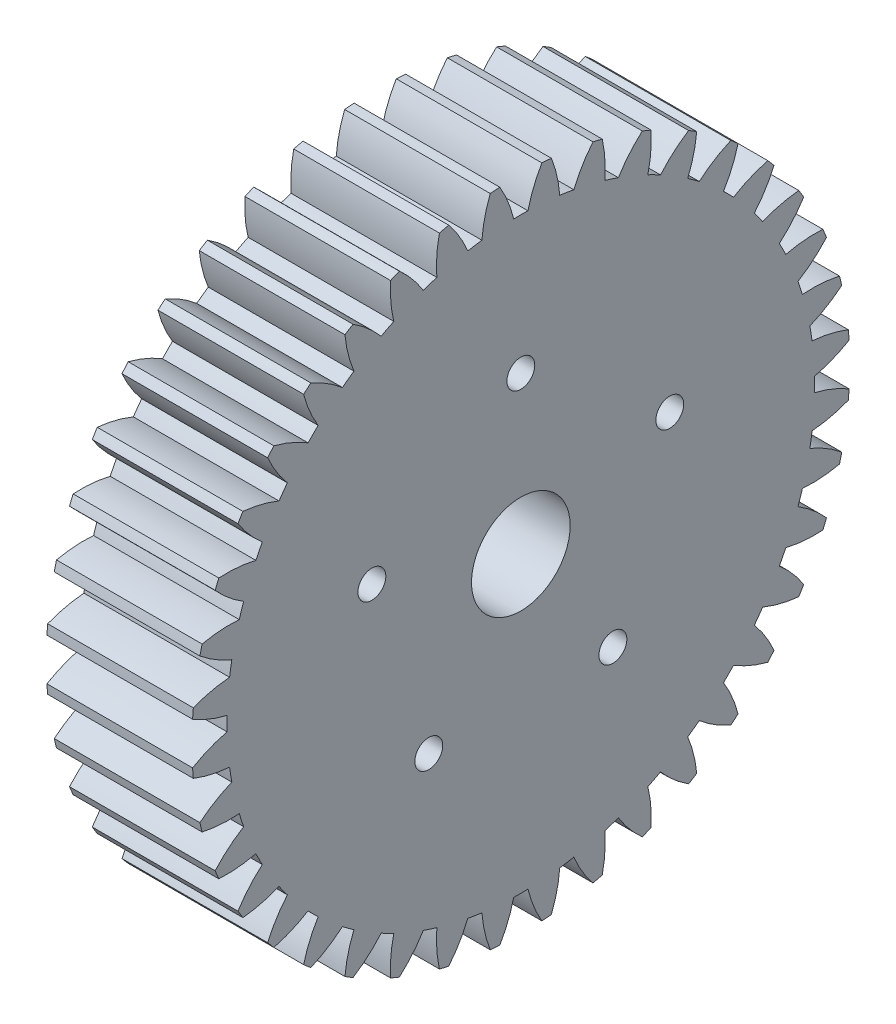
SolidWorks part; units mm, degrees
ref_plane "Plane1" through (0, 0, 0) normal (0, 0, 1) x (1, 0, 0)
ref_plane "Plane2" through (0, 0, 0) normal (0, 1, 0) x (1, 0, 0)
ref_plane "Plane3" through (0, 0, 0) normal (1, 0, 0) x (0, 0, -1)
sketch "HoldingSke" plane through (0, 0, 0) normal (0, 1, 0) x (1, 0, 0)
  line L0 (0, 0) -> (389.1506, -326.5361)
  line L1 (-15, 0) -> (100, 0) construction
  line L2 (0, 0) -> (-2.1039, 2.3779)
  line L3 (0, 0) -> (-11.863, 4.5341)
  line L4 (0, 0) -> (6.6156, 5.5511)
  line L5 (0, 0) -> (-47.5972, -17.7524)
  line L6 (0, 0) -> (-9.7909, -6.6059)
  line L7 (-2.1039, 2.3779) -> (8.8308, 51.9871)
  line L8 (-76.2, 54.61) -> (-75.184, 54.61)
  line L9 (-71.009, 38.7566) -> (-53.1078, 45.2721)
  line L10 (-76.2, 71.12) -> (104.1128, 71.12)
  line L11 (0, 0) -> (-11.811, 0)
  line L12 (-76.2, 101.6) -> (-76.1492, 101.6)
  line L13 (24.9733, 27.94) -> (52.9518, 28.4284)
  line L14 (24.9733, 27.94) -> (25.0241, 27.9398)
  line L15 (24.9733, 27.94) -> (100.4021, 29.52)
  circle A0 centre (0, 0) radius 0.3969
  circle A1 centre (0, 0) radius 23.8252
  circle A2 centre (0, 0) radius 38.1
  circle A3 centre (0, 0) radius 0.3969
  dimension "MHD" = 47.6504
  dimension "Hub_dia" = 76.2
  dimension "Bore" = 0.7937
  dimension "MBD" = 0.7937
  dimension "Num_teeth" = 40
  dimension "Pitch_radius" = 180.3128
  dimension "Pitch" = 508
  dimension "Width" = 11.811
  dimension "Overall_len" = 50.8
  dimension "Show_teeth" = 40
  dimension "Thickness" = 11.811
  dimension "OAL" = 50.8001
  dimension "T_dim" = 1.016
  dimension "Ap" = 20
  dimension "H" = 19.05
  dimension "Backlash" = 0.0508
  dimension "Addendum_fac" = 1
  dimension "Dedendum_fac" = 1.2
  dimension "Clearance_fac" = 0.2
  dimension "Dedendum_add" = 0.0508
sketch "BasProSke" plane through (0, 0, 0) normal (0, 1, 0) x (1, 0, 0)
  line L0 (-10, 0) -> (60, 0) construction
  line L1 (0, 0) -> (0, 26.67)
  line L2 (0, 0) -> (11.811, 0)
  line L3 (11.811, 0) -> (11.811, 26.67)
  line L4 (11.811, 26.67) -> (0, 26.67)
  dimension "Diameter" = 53.34
  dimension "Thickness" = 11.811
revolve "Base-Revolve" add sketch "BasProSke" angle 360 about L0
sketch "TooCutSke" plane through (0, 0, 0) normal (1, 0, 0) x (0, 0, -1)
  line L1 (0, 0) -> (0, 107) construction
  line L2 (0, 0) -> (-1.0861, 25.3768) construction
  line L3 (0, 0) -> (-3.9832, 50.611) construction
  line L4 (-1.0861, 25.3768) -> (-1.9916, 25.3055) construction
  arc A0 (0.5773, 23.8182) -> (-0.5773, 23.8182) centre (0, 0) ccw
  arc A1 (1.7213, 26.6399) -> (-1.7213, 26.6399) centre (0, 0) ccw
  circle A2 centre (0, 0) radius 25.4 construction
  circle A3 centre (0, 0) radius 23.8682 construction
  arc A4 (-0.5773, 23.8182) -> (-1.7213, 26.6399) centre (-10.4586, 21.4548) ccw
  arc A5 (1.7213, 26.6399) -> (0.5773, 23.8182) centre (10.4586, 21.4548) ccw
  dimension "Root_dia" = 47.6504
  dimension "Overcut_dia" = 53.3908
  dimension "Pitch_dia" = 50.8
  dimension "Base_dia" = 47.7364
  dimension "Flank_rad" = 10.16
  dimension "Half_ang" = 4.5
  dimension "Half_CT" = 0.9083
extrude "ToothCut" cut sketch "TooCutSke" along normal through all
fillet "Breaks" [suppressed] radius 0.0254 tangent propagation no
fillet "RootFillets" [suppressed] radius 0.3048
pattern_circular "TeethCuts" count 40 every 9 about axis through (-10, 0, 0) along (1, 0, 0) of "ToothCut", "RootFillets", "Breaks"
sketch "HubNeaOneSke" plane through (0, 0, 0) normal (-1, 0, 0) x (0, 0, 1)
  circle A0 centre (0, 0) radius 23.8252
  dimension "Diameter" = 47.6504
extrude "HubNearOne" [suppressed] add sketch "HubNeaOneSke" along normal blind 38.9891
sketch "HubNeaBotSke" plane through (0, 0, 0) normal (-1, 0, 0) x (0, 0, 1)
  circle A0 centre (0, 0) radius 23.8252
  dimension "Diameter" = 47.6504
extrude "HubNearBoth" [suppressed] add sketch "HubNeaBotSke" along normal blind 19.4945
ref_plane "FarPln" through (11.811, 0, 0) normal (1, 0, 0) x (0, 0, -1)
sketch "HubFarSke" plane through (11.811, 0, 0) normal (1, 0, 0) x (0, 0, -1)
  circle A0 centre (0, 0) radius 23.8252
  dimension "Diameter" = 47.6504
extrude "HubFar" [suppressed] add sketch "HubFarSke" along normal blind 19.4945
sketch "BorSke" plane through (0, 0, 0) normal (1, 0, 0) x (0, 0, -1)
  circle A0 centre (0, 0) radius 0.3969
  dimension "Diameter" = 0.7937
extrude "Bore" cut sketch "BorSke" along normal mid plane 101.6001
sketch "KeySke" plane through (0, 0, 0) normal (1, 0, 0) x (0, 0, -1)
  line L0 (-0.127, 0) -> (-0.127, 0.6191)
  line L1 (-0.127, 0.6191) -> (0.127, 0.6191)
  line L2 (0.127, 0.6191) -> (0.127, 0)
  line L3 (0, 0) -> (0, 34) construction
  line L4 (-0.127, 0) -> (0.127, 0)
  dimension "Offset" = 0.6191
  dimension "Width" = 0.254
extrude "Keyway" [suppressed] cut sketch "KeySke" along normal mid plane 101.6001
pattern_circular "Keyway2" [suppressed] count 2 every 90 about axis through (-10, 0, 0) along (1, 0, 0)
sketch "Sketch3" plane through (11.811, 0, 0) normal (1, 0, 0) x (0, 0, -1)
  line L0 (0, 0) -> (0, 29.4974) construction
  circle A0 centre (0, 0) radius 4
  circle A1 centre (0, 12.7) radius 1.1303
  circle A2 centre (12.0784, 3.9245) radius 1.1303
  circle A3 centre (7.4649, -10.2745) radius 1.1303
  circle A4 centre (-7.4649, -10.2745) radius 1.1303
  circle A5 centre (-12.0784, 3.9245) radius 1.1303
  point P16 (0, 0)
  dimension "D1" = 8
  dimension "D2" = 2.2606
  dimension "D3" = 12.7
  dimension "D4" = 5
extrude "Cut-Extrude1" cut sketch "Sketch3" against normal blind 15.748
equation "' \"Pitch@HoldingSke\" = 4"
equation "' \"Num_teeth@HoldingSke\" = 12"
equation "' \"Ap@HoldingSke\" =  20"
equation "' \"Width@HoldingSke\" = 0.5"
equation "' \"Hub_dia@HoldingSke\"= 1"
equation "' \"Overall_len@HoldingSke\" = 1.0"
equation "' \"Bore@HoldingSke\" = 0.75"
equation "' \"T_dim@HoldingSke\" = 0.85"
equation "' \"Width@KeySke\" = 0.25"
equation "' \"Show_teeth@HoldingSke\" = 13"
equation "' \"Backlash@HoldingSke\" = 0.009"
equation "' \"Addendum_fac@HoldingSke\" = 1.0"
equation "' \"Dedendum_fac@HoldingSke\" = 1.25"
equation "' \"Dedendum_add@HoldingSke\" = 0.00005"
equation "' \"Clearance_fac@HoldingSke\" = 0.25"
equation "' \"Pitch@HoldingSke\" = 0.5"
equation "' \"Num_teeth@HoldingSke\" = 23"
equation "' \"Show_teeth@HoldingSke\" = 23"
equation "' \"Backlash@HoldingSke\" = 0.0375"
equation "\"Overcut_dia@TooCutSke\" = (\"Num_teeth@HoldingSke\" + 2 * \"Addendum_fac@HoldingSke\") / \"Pitch@HoldingSke\" + 0.002"
equation "\"Pitch_dia@TooCutSke\" = \"Num_teeth@HoldingSke\" / \"Pitch@HoldingSke\""
equation "\"Base_dia@TooCutSke\" = \"Num_teeth@HoldingSke\" / \"Pitch@HoldingSke\" * cos((\"Ap@HoldingSke\"  * 3.14159265 / 180))"
equation "\"Root_dia@TooCutSke\" = (\"Num_teeth@HoldingSke\" + 2) / \"Pitch@HoldingSke\" - 2 * (\"Addendum_fac@HoldingSke\" + \"Dedendum_fac@HoldingSke\") / \"Pitch@HoldingSke\" - \"Dedendum_add@HoldingSke\" * 2"
equation "\"Half_ang@TooCutSke\" = 180 / \"Num_teeth@HoldingSke\""
equation "\"Half_CT@TooCutSke\" = \"Num_teeth@HoldingSke\" / \"Pitch@HoldingSke\" * sin((3.14159265 / 2 / \"Num_teeth@HoldingSke\")) / 2 - 7 * \"Backlash@HoldingSke\" / 4"
equation "\"Flank_rad@TooCutSke\" = \"Num_teeth@HoldingSke\" / \"Pitch@HoldingSke\" / 5"
equation "\"Radius@RootFillets\" = \"Clearance_fac@HoldingSke\" / \"Pitch@HoldingSke\" + \"Dedendum_add@HoldingSke\""
equation "\"Break_rad@Breaks\" = 0.02 / \"Pitch@HoldingSke\""
equation "\"Thickness@HoldingSke\" = \"Width@HoldingSke\""
equation "\"OAL@HoldingSke\" = \"Thickness@HoldingSke\""
equation "\"MHD@HoldingSke\" = (\"Num_teeth@HoldingSke\" + 2) / \"Pitch@HoldingSke\" - 2 * (\"Addendum_fac@HoldingSke\" + \"Dedendum_fac@HoldingSke\")  / \"Pitch@HoldingSke\" - \"Dedendum_add@HoldingSke\" * 2"
equation "\"MBD@HoldingSke\" = (\"Num_teeth@HoldingSke\" + 2) / \"Pitch@HoldingSke\" - 2 * (\"Addendum_fac@HoldingSke\" + \"Dedendum_fac@HoldingSke\")  / \"Pitch@HoldingSke\" - \"Dedendum_add@HoldingSke\" * 2 - 0.002"
equation "\"MHD@HoldingSke\" = ((sgn( \"MHD@HoldingSke\" - \"Hub_dia@HoldingSke\" )-1)*( \"MHD@HoldingSke\" - \"Hub_dia@HoldingSke\" ))/-2+ \"Hub_dia@HoldingSke\""
equation "\"MBD@HoldingSke\" = ((sgn( \"MBD@HoldingSke\" - \"Bore@HoldingSke\" )-1)*( \"MBD@HoldingSke\" - \"Bore@HoldingSke\" ))/-2+ \"Bore@HoldingSke\""
equation "\"OAL@HoldingSke\" = ((sgn( \"OAL@HoldingSke\" - \"Overall_len@HoldingSke\" )+1)*( \"OAL@HoldingSke\" - \"Overall_len@HoldingSke\" ))/2 + \"Overall_len@HoldingSke\" + 0.000002"
equation "\"Num_teeth@TeethCuts\" = int( \"Show_teeth@HoldingSke\" ) + 1"
equation "\"Num_teeth@TeethCuts\" = ((sgn( \"Num_teeth@TeethCuts\" - \"Num_teeth@HoldingSke\" )-1)*( \"Num_teeth@TeethCuts\" - \"Num_teeth@HoldingSke\" ))/-2+ \"Num_teeth@HoldingSke\""
equation "\"Num_teeth@TeethCuts\" = ((sgn( \"Num_teeth@TeethCuts\" - 2.0)+1)*( \"Num_teeth@TeethCuts\" - 2.0))/2 +2.0"
equation "\"Angle@TeethCuts\" = 360.0 / \"Num_teeth@HoldingSke\""
equation "\"Diameter@BasProSke\" = (\"Num_teeth@HoldingSke\" + 2 * \"Addendum_fac@HoldingSke\") / \"Pitch@HoldingSke\""
equation "\"Thickness@BasProSke\"  = \"Thickness@HoldingSke\""
equation "' \"Fillet_rad@BasProSke\" =  \"Thickness@HoldingSke\" * 0.05"
equation "\"MHD@HoldingSke\" = ((sgn( \"MHD@HoldingSke\" - \"Root_dia@TooCutSke\" )-1)*( \"MHD@HoldingSke\" - \"Root_dia@TooCutSke\" ))/-2+ \"Root_dia@TooCutSke\""
equation "\"Diameter@HubNeaOneSke\" = \"MHD@HoldingSke\""
equation "\"Length@HubNearOne\" = \"OAL@HoldingSke\" - \"Thickness@BasProSke\""
equation "\"Diameter@HubNeaBotSke\" = \"MHD@HoldingSke\""
equation "\"Length@HubNearBoth\" = ( \"OAL@HoldingSke\" - \"Thickness@BasProSke\" ) / 2.0"
equation "\"Thickness@FarPln\" = \"Thickness@BasProSke\""
equation "\"Diameter@HubFarSke\" = \"MHD@HoldingSke\""
equation "\"Length@HubFar\" = ( \"OAL@HoldingSke\" - \"Thickness@BasProSke\" ) / 2.0"
equation "\"Diameter@BorSke\" = \"MBD@HoldingSke\""
equation "\"D1@Bore\" = \"OAL@HoldingSke\" * 2.0"
equation "\"D1@Keyway\" = \"OAL@HoldingSke\" * 2.0"
equation "\"Offset@KeySke\" = \"T_dim@HoldingSke\" - \"MBD@HoldingSke\" / 2.0"
